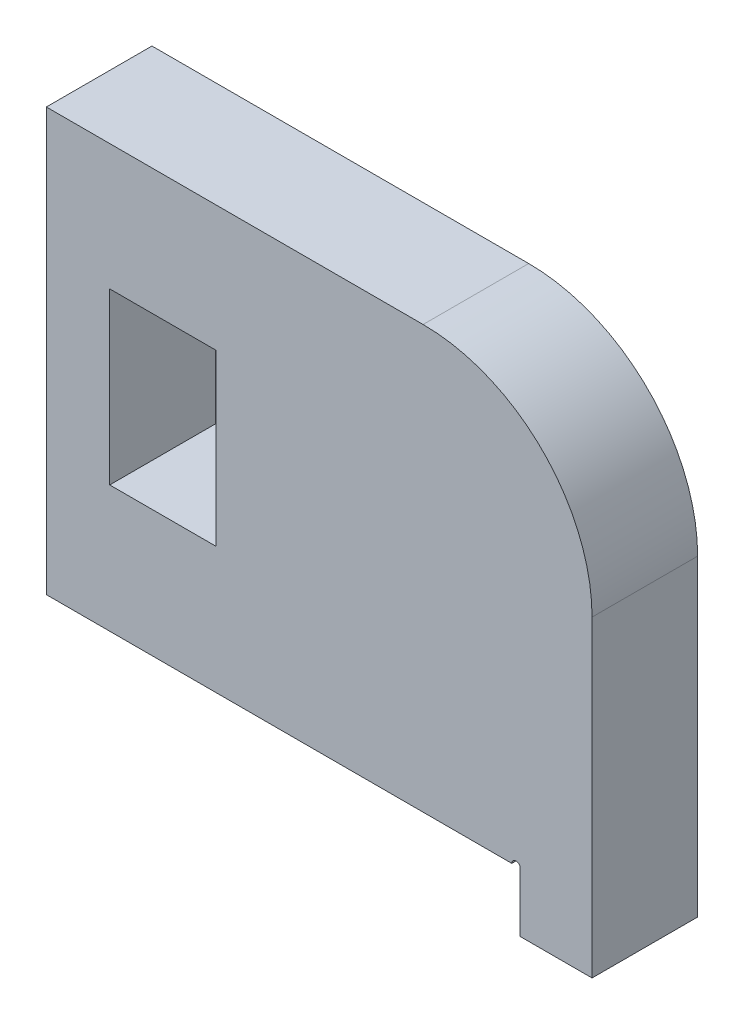
SolidWorks part; units mm, degrees
material "PBT General Purpose"
ref_plane "Front Plane" through (0, 0, 0) normal (0, 0, 1) x (1, 0, 0)
ref_plane "Top Plane" through (0, 0, 0) normal (0, 1, 0) x (1, 0, 0)
ref_plane "Right Plane" through (0, 0, 0) normal (1, 0, 0) x (0, 0, -1)
sketch "frame_outline" plane through (0, 0, 0) normal (0, 0, 1) x (1, 0, 0)
  line L110 (0, 0) -> (0, 1)
  line L121 (0.302, 0) -> (0, 0)
  line L122 (0, 1) -> (1.292, 1)
  line L123 (1.292, 1) -> (1.292, -0.14)
  line L124 (1.292, -0.14) -> (1.122, -0.14)
  line L125 (1.122, -0.14) -> (1.122, 0.01)
  line L126 (1.122, 0.01) -> (1.102, 0.01)
  line L127 (1.102, 0.01) -> (1.102, 0)
  line L128 (1.102, 0) -> (0.302, 0)
  line L131 (0.15, 0.702) -> (0.402, 0.702)
  line L132 (0.15, 0.702) -> (0.15, 0.3)
  line L133 (0.15, 0.3) -> (0.402, 0.3)
  line L134 (0.402, 0.702) -> (0.402, 0.3)
  dimension "D1" = 1
  dimension "D2" = 0.3
  dimension "D3" = 0.252
  dimension "D4" = 0.402
  dimension "D5" = 0.17
  dimension "D6" = 0.8
  dimension "D7" = 0.15
  dimension "D8" = 0.01
  dimension "D9" = 0.02
  dimension "D10" = 0.7
  dimension "D11" = 0.15
extrude "Boss-Extrude1" add sketch "frame_outline" along normal mid plane 0.25
fillet "Fillet1" radius 0.01 2 edges at (1.122, 0.01, 0) (1.102, 0.01, 0)
fillet "Fillet2" radius 0.4 1 edges at (1.292, 1, 0)
equation "\"t\"= 0.25'thickness of the sheets"
equation "\"t_cf\"= 0.115'thickness of single carbon fiber layer"
equation "\"t_kapton\"= 0.025'thickness of single Kapton flex layer"
equation "\"t_fr4\"= 0.1'thickness of FR4 with copper layer"
equation "\"joint_flex\"= 0.1'Width of flextures gap"
equation "\"joint_flex_eff\"= 0.02'Width of flecture after castelation"
equation "\"joint_fold\"= 0.2'Width of folding joints for 90deg fold"
equation "\"gap_tolerance\"= 0.002'Width to have interfecence fit between carbon fiber inserts"
equation "\"assemble_angle\"= 90'Angle of assembly parts"
equation "\"D1@Boss-Extrude1\"=\"t\""
equation "\"link_lift\"= 0.5'Actuation linkage amplification for the lift motion"
equation "\"link_swing\"= 0.45'Actuation linkage amplification for the swing motion"
equation "\"D3@frame_outline\"=\"t\"+\"gap_tolerance\""
equation "\"D4@frame_outline\"=0.4+\"gap_tolerance\""
equation "\"D5@frame_outline\"=0.17"
equation "\"D7@frame_outline\"=\"joint_fold\"-0.05"
